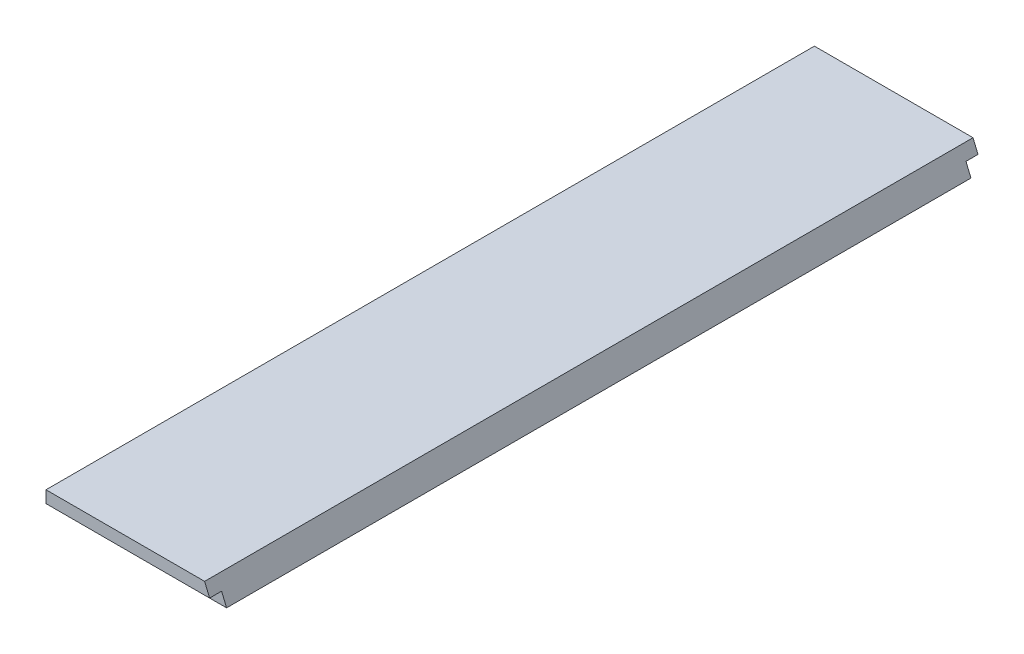
SolidWorks part; units mm, degrees
ref_plane "Front Plane" through (0, 0, 0) normal (0, 0, 1) x (1, 0, 0)
ref_plane "Top Plane" through (0, 0, 0) normal (0, 1, 0) x (1, 0, 0)
ref_plane "Right Plane" through (0, 0, 0) normal (1, 0, 0) x (0, 0, -1)
sketch "Sketch1" plane through (0, 0, 0) normal (0, 0, 1) x (1, 0, 0)
  line L0 (0, 0) -> (0, 12.7)
  line L1 (0, 12.7) -> (83.8935, 12.7)
  line L2 (83.8935, 12.7) -> (89.154, 0)
  line L3 (89.154, 0) -> (0, 0)
  dimension "D1" = 12.7
  dimension "D2" = 67.5
  dimension "D3" = 89.154
extrude "Boss-Extrude1" add sketch "Sketch1" along normal blind 406.4
sketch "Sketch2" plane through (0, 0, 0) normal (0, -1, 0) x (1, 0, 0)
  line L0 (0, 406.4) -> (0, 0) construction
  line L1 (0, 6.35) -> (89.154, 6.35)
  line L2 (0, 6.35) -> (0, 0)
  line L3 (0, 0) -> (89.154, 0)
  line L4 (89.154, 6.35) -> (89.154, 0)
  line L5 (89.154, 406.4) -> (89.154, 0) construction
  line L6 (0, 406.4) -> (89.154, 406.4)
  line L7 (0, 406.4) -> (0, 400.05)
  line L8 (0, 400.05) -> (89.154, 400.05)
  line L9 (89.154, 406.4) -> (89.154, 400.05)
  dimension "D1" = 6.35
  dimension "D2" = 6.35
extrude "Cut-Extrude1" cut sketch "Sketch2" against normal blind 6.35
